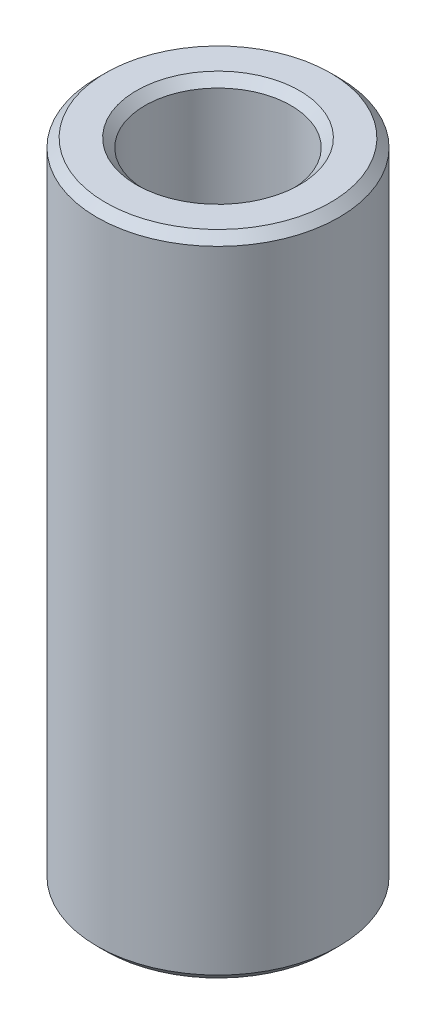
SolidWorks part; units mm, degrees
ref_plane "Front Plane" through (0, 0, 0) normal (0, 0, 1) x (1, 0, 0)
ref_plane "Top Plane" through (0, 0, 0) normal (0, 1, 0) x (1, 0, 0)
ref_plane "Right Plane" through (0, 0, 0) normal (1, 0, 0) x (0, 0, -1)
sketch "Sketch1" plane through (0, 0, 0) normal (0, 1, 0) x (1, 0, 0)
  circle A0 centre (0, 0) radius 40
  dimension "SLEEVE_OD" = 80
extrude "Boss-Extrude1" add sketch "Sketch1" along normal blind 214.3725
sketch "Sketch2" plane through (0, 0, 0) normal (0, 1, 0) x (1, 0, 0)
  circle A0 centre (0, 0) radius 24.149
  dimension "BORE_D" = 48.298
extrude "Cut-Extrude1" cut sketch "Sketch2" along normal through all
chamfer "Chamfer1" distance 2.837 angle 45 4 edges at (0, 214.3725, 24.149) (0, 0, 24.149) (0, 0, 40) (0, 214.3725, 40)
